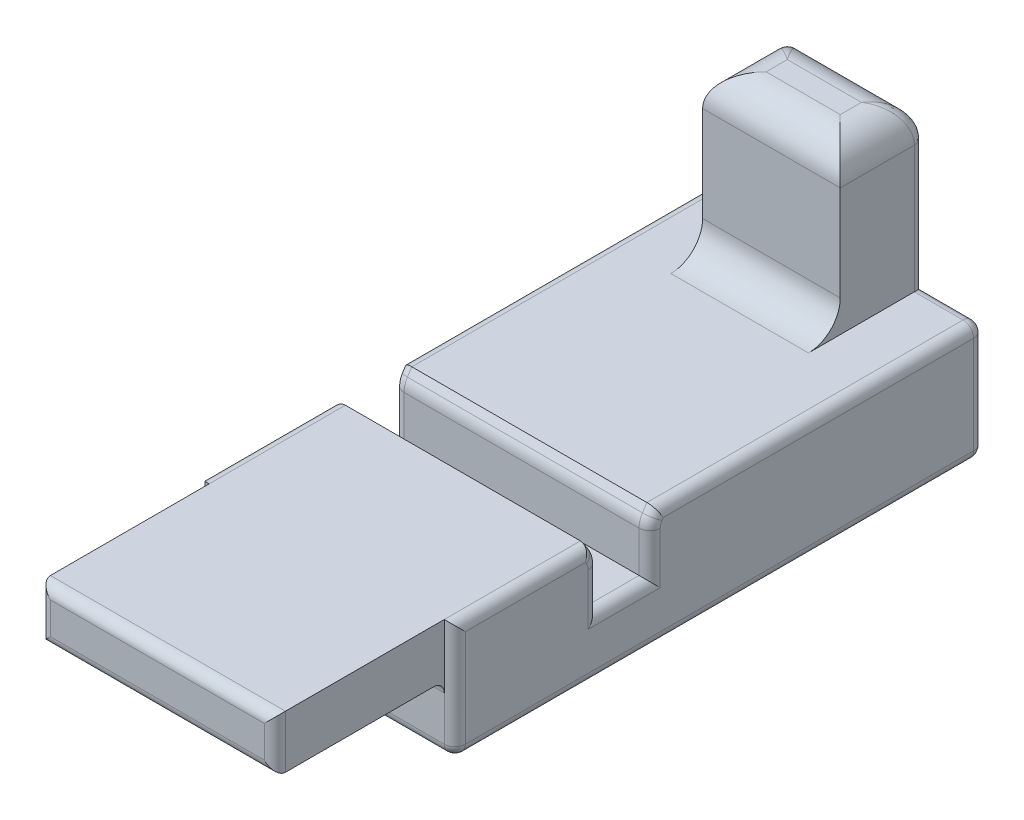
SolidWorks part; units mm, degrees
ref_plane "Front Plane" through (0, 0, 0) normal (0, 0, 1) x (1, 0, 0)
ref_plane "Top Plane" through (0, 0, 0) normal (0, 1, 0) x (1, 0, 0)
ref_plane "Right Plane" through (0, 0, 0) normal (1, 0, 0) x (0, 0, -1)
sketch "Sketch1" plane through (0, 0, 0) normal (0, 0, 1) x (1, 0, 0)
  line L15 (-29.4907, 17.9886) -> (-14.4907, 17.9886)
  line L25 (-14.4907, 17.9886) -> (-10.0907, 17.9886)
  line L26 (-10.0907, 17.9886) -> (-10.0907, 6.7886)
  line L27 (-10.0907, 6.7886) -> (-34.2907, 6.7886)
  line L28 (-34.2907, 6.7886) -> (-34.2907, 17.9886)
  line L29 (-34.2907, 17.9886) -> (-29.4907, 17.9886)
  dimension "D1" = 24.2
  dimension "D2" = 11.2
extrude "Boss-Extrude1" add sketch "Sketch1" against normal blind 50
sketch "Sketch2" plane through (-34.2907, 0, 0) normal (-1, 0, 0) x (0, 0, 1)
  line L0 (-16, 17.9886) -> (-16, 6.7886) construction
  line L1 (-50, 17.9886) -> (0, 17.9886) construction
  line L2 (-50, 6.7886) -> (0, 6.7886) construction
  line L3 (-50, 6.7886) -> (-50, 17.9886) construction
  line L4 (-18.4, 16.2601) -> (-18.4, 12.3886)
  line L8 (-13.6, 12.3886) -> (-18.4, 12.3886)
  line L10 (-19.3, 18.2352) -> (-18.7245, 17.3522)
  line L12 (-13.6, 16.2601) -> (-13.6, 12.3886)
  line L13 (-12.7, 18.2352) -> (-13.2755, 17.3522)
  line L15 (-19.3, 18.2352) -> (-12.7, 18.2352)
  arc A0 (-18.4, 16.2601) -> (-18.7245, 17.3522) centre (-20.4, 16.2601) ccw
  arc A1 (-13.6, 16.2601) -> (-13.2755, 17.3522) centre (-11.6, 16.2601) cw
  point P13 (-16, 12.3886)
  point P17 (-16, 12.3886)
  dimension "D2" = 2
  dimension "D1" = 34
  dimension "D3" = 2.4
  dimension "D4" = 3.3
extrude "Cut-Extrude1" cut sketch "Sketch2" against normal through all
sketch "Sketch3" plane through (0, 17.9886, 0) normal (0, 1, 0) x (1, 0, 0)
  line L0 (-22.1907, 50) -> (-22.1907, 0) construction
  line L1 (-10.0907, 50) -> (-34.2907, 50) construction
  line L2 (-10.0907, 0) -> (-34.2907, 0) construction
  line L4 (-15.6907, 42) -> (-28.6907, 42)
  line L5 (-15.6907, 42) -> (-15.6907, 50)
  line L6 (-15.6907, 50) -> (-28.6907, 50)
  line L7 (-28.6907, 42) -> (-28.6907, 50)
  line L8 (-15.6907, 42) -> (-28.6907, 50) construction
  line L9 (-15.6907, 50) -> (-28.6907, 42) construction
  point P6 (-22.1907, 46)
  dimension "D1" = 13
  dimension "D2" = 8
extrude "Boss-Extrude2" add sketch "Sketch3" along normal blind 15
fillet "Fillet1" radius 3 5 edges at (-22.1907, 32.9886, -50) (-15.6907, 32.9886, -46) (-22.1907, 32.9886, -42) (-28.6907, 32.9886, -46) (-22.1907, 17.9886, -42)
fillet "Fillet2" radius 1 30 edges at (-16.5694, 32.1099, -49.1213) (-27.812, 32.1099, -49.1213) (-34.2907, 16.8297, -18.4828) (-34.2907, 14.3243, -18.4) (-34.2907, 12.3886, -16) (-34.2907, 14.3243, -13.6) (-34.2907, 16.8297, -13.5172) (-34.2907, 17.6704, -13.0681) (-34.2907, 17.9886, -34.5696) (-34.2907, 12.3886, 0) (-34.2907, 17.6704, -18.9319) (-34.2907, 6.7886, -25) (-22.1907, 6.7886, 0) (-10.0907, 17.9886, -34.5696) (-10.0907, 6.7886, -25) (-10.0907, 12.3886, 0) (-10.0907, 17.6704, -13.0681) (-10.0907, 16.8297, -13.5172) (-10.0907, 14.3243, -13.6) (-10.0907, 12.3886, -16) (-10.0907, 14.3243, -18.4) (-10.0907, 16.8297, -18.4828) (-10.0907, 17.6704, -18.9319) (-31.4907, 17.9886, -50) (-34.2907, 12.3886, -50) (-22.1907, 6.7886, -50) (-10.0907, 12.3886, -50) (-12.8907, 17.9886, -50) (-15.6907, 23.9886, -50) (-28.6907, 23.9886, -50)
sketch "Sketch4" plane through (0, 0, 0) normal (0, 0, 1) x (1, 0, 0)
  line L0 (-33.2907, 17.9886) -> (-33.2907, 7.7886) construction
  line L1 (-33.2907, 17.9886) -> (-11.0907, 17.9886)
  line L2 (-33.2907, 17.9886) -> (-33.2907, 12.9886)
  line L3 (-33.2907, 12.9886) -> (-11.0907, 12.9886)
  line L4 (-11.0907, 17.9886) -> (-11.0907, 12.9886)
  line L5 (-11.0907, 17.9886) -> (-33.2907, 17.9886) construction
  line L6 (-11.0907, 7.7886) -> (-11.0907, 17.9886) construction
  dimension "D1" = 5
extrude "Boss-Extrude3" add sketch "Sketch4" along normal blind 16
fillet "Fillet3" radius 1 5 edges at (-22.1907, 17.9886, 16) (-11.0907, 15.4886, 16) (-22.1907, 12.9886, 16) (-33.2907, 15.4886, 16) (-22.1907, 12.9886, 0)
